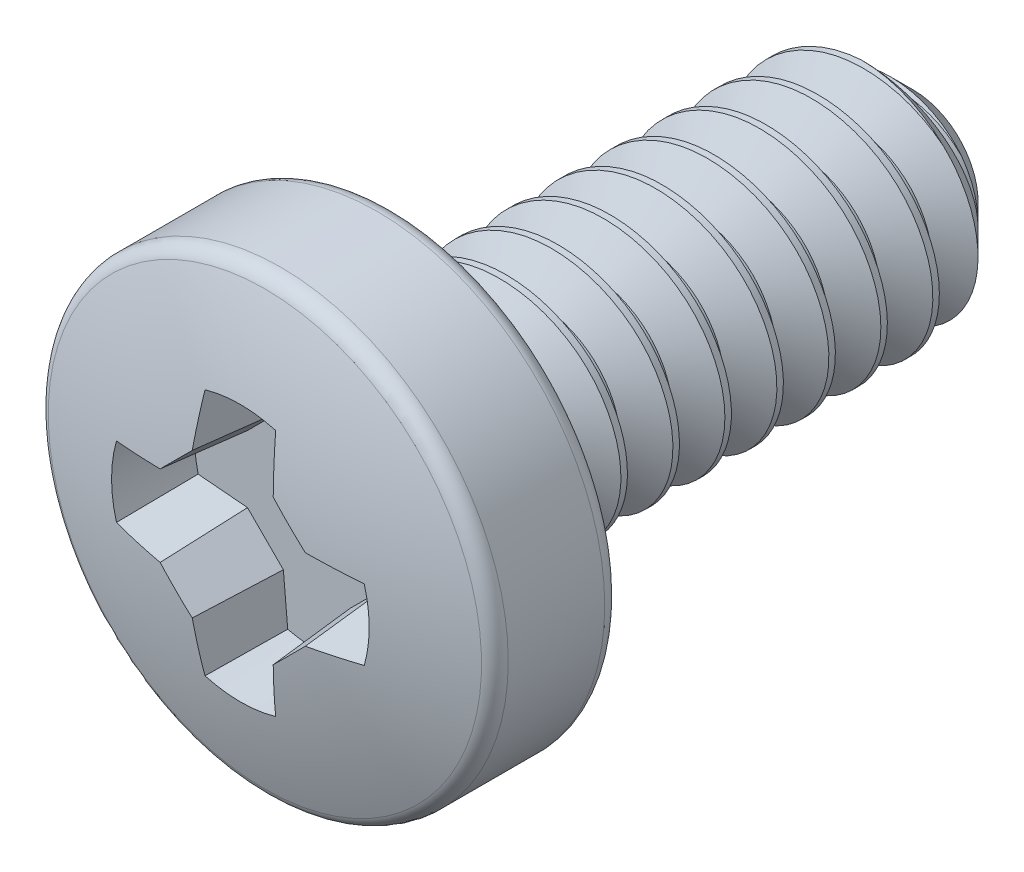
SolidWorks part; units mm, degrees
ref_plane "Front Plane" through (0, 0, 0) normal (0, 0, 1) x (1, 0, 0)
ref_plane "Top Plane" through (0, 0, 0) normal (0, 1, 0) x (1, 0, 0)
ref_plane "Right Plane" through (0, 0, 0) normal (1, 0, 0) x (0, 0, -1)
sketch "Layout_Sketch1" plane through (0, 0, 0) normal (1, 0, 0) x (0, 0, -1)
  line L0 (0, -2.7813) -> (0, 2.7813) construction
  line L1 (6.35, -1.4224) -> (6.35, 1.4224) construction
  line L2 (6.35, 0) -> (-2.032, 0) construction
  line L3 (-1.524, 2.7813) -> (0, 2.7813)
  line L4 (-1.524, -2.7813) -> (0, -2.7813)
  line L5 (6.35, 1.4224) -> (0, 1.4224) construction
  line L6 (6.35, -1.4224) -> (5.715, -1.4224) construction
  arc A0 (-1.524, -2.7813) -> (-1.524, 2.7813) centre (5.8358, 0) cw
  point P4 (0, 0)
  point P8 (6.35, 0)
  point P13 (5.3975, 0.4953)
  point P16 (5.715, -1.4224)
  point P17 (-0.9398, 0)
  point P18 (-0.635, 0)
  dimension "HeadDIA" = 5.5626
  dimension "HeadH" = 2.032
  dimension "D1" = 1.524
  dimension "ThreadOD" = 2.8448
  dimension "ThreadPitch" = 0.635
  dimension "D3" = 0.9525
  dimension "D2" = 0.635
  dimension "D4" = 0.3048
  dimension "D5" = 6.985
  dimension "ThreadLength" = 6.35
sketch "Sketch2" plane through (0, 0, 0) normal (1, 0, 0) x (0, 0, -1)
  line L0 (-1.524, 2.7813) -> (0, 2.7813)
  line L1 (0, 2.7813) -> (0, 1.4224)
  line L2 (0, 1.4224) -> (6.35, 1.4224)
  line L3 (6.35, 1.4224) -> (6.35, 0)
  line L4 (6.35, -1.4224) -> (6.35, 1.4224) construction
  line L5 (6.35, 0) -> (-2.032, 0)
  arc A0 (-2.032, 0) -> (-1.524, 2.7813) centre (5.8358, 0) cw
  arc A1 (-1.524, 2.7813) -> (-1.524, -2.7813) centre (5.8358, 0) ccw construction
revolve "Revolve1" add sketch "Sketch2" angle 360 about L5
ref_plane "Plane1" through (0, 0, 2.032) normal (0, 0, 1) x (1, 0, 0)
sketch "Sketch3" plane through (0, 0, 2.032) normal (0, 0, 1) x (1, 0, 0)
  line L0 (0, 0) -> (0, 0.889) construction
  line L1 (0, -2.7813) -> (0, 2.7813) construction
  line L2 (-0.4445, 0) -> (0.4445, 0) construction
  line L3 (0, 0) -> (1.5875, 0) construction
  line L4 (0.4445, 1.524) -> (0.5001, 0.889)
  line L5 (0.889, 0.5001) -> (1.524, 0.4445)
  line L6 (0, 0) -> (0.6286, 0.6286) construction
  line L7 (0.5001, 0.889) -> (0.889, 0.5001)
  line L8 (0.6945, 0.6945) -> (0.6286, 0.6286) construction
  line L9 (0.4445, 1.524) -> (0.4445, 0.7699) construction
  line L10 (0.889, -0.5001) -> (1.524, -0.4445)
  line L11 (0.5001, -0.889) -> (0.889, -0.5001)
  line L12 (0.4445, -1.524) -> (0.5001, -0.889)
  line L13 (-0.4445, -1.524) -> (-0.5001, -0.889)
  line L14 (-0.5001, -0.889) -> (-0.889, -0.5001)
  line L15 (-0.889, -0.5001) -> (-1.524, -0.4445)
  line L16 (-0.889, 0.5001) -> (-1.524, 0.4445)
  line L17 (-0.5001, 0.889) -> (-0.889, 0.5001)
  line L18 (-0.4445, 1.524) -> (-0.5001, 0.889)
  circle A0 centre (0, 0) radius 1.5875 construction
  circle A1 centre (0, 0) radius 0.889 construction
  arc A2 (-0.4445, 1.524) -> (0.4445, 1.524) centre (0, 0) cw
  arc A3 (1.524, 0.4445) -> (1.524, -0.4445) centre (0, 0) cw
  arc A4 (-1.524, 0.4445) -> (-1.524, -0.4445) centre (0, 0) ccw
  arc A5 (-0.4445, -1.524) -> (0.4445, -1.524) centre (0, 0) ccw
  point P9 (0, 0)
  point P21 (0, -1.5875)
  dimension "Phil_DIA" = 3.175
  dimension "Phil_W" = 0.889
  dimension "D1" = 45
  dimension "D2" = 0.889
  dimension "D3" = 5
extrude "Cut-Extrude1" cut sketch "Sketch3" against normal up to vertex (1.0922 mm away) draft 5 up to point (0, 0, 0.9398)
fillet "Fillet1" radius 0.2032 2 edges at (0, 2.7813, 0) (0, 2.7813, 1.524)
chamfer "Chamfer1" distance 0.635 angle 45 1 edges at (0, 1.4224, -6.35)
sketch "Sketch4" plane through (0, 0, 0) normal (1, 0, 0) x (0, 0, -1)
  line L0 (6.3103, 1.4911) -> (6.9453, 1.4911) construction
  line L1 (6.9453, 1.4911) -> (6.6278, 0.9412) construction
  line L2 (6.6278, 0.9412) -> (6.3103, 1.4911) construction
  line L3 (6.6278, 0.9412) -> (6.6278, 1.01) construction
  line L4 (6.6278, 1.01) -> (6.6278, 1.4224) construction
  line L5 (6.6278, 1.4224) -> (6.6278, 1.4911) construction
  line L6 (6.9255, 1.4568) -> (6.3302, 1.4568) construction
  line L7 (6.9056, 1.4224) -> (6.35, 1.4224) construction
  line L8 (6.6675, 1.01) -> (6.5881, 1.01) construction
  line L9 (6.3302, 1.4568) -> (6.9255, 1.4568)
  line L10 (6.9255, 1.4568) -> (6.6675, 1.01)
  line L11 (6.6675, 1.01) -> (6.5881, 1.01)
  line L12 (6.5881, 1.01) -> (6.3302, 1.4568)
  line L13 (6.35, -1.4224) -> (6.35, 1.4224) construction
  line L14 (6.35, 1.4224) -> (0, 1.4224) construction
  point P9 (6.6278, 1.4224)
  point P12 (6.6278, 1.4568)
  point P15 (6.6278, 1.01)
  dimension "D1" = 0.635
  dimension "D2" = 0.0794
sketch "Sketch5" plane through (0, 0, -6.35) normal (0, 0, -1) x (-1, 0, 0)
  circle A0 centre (0, 0) radius 1.4224
curve "Helix/Spiral1" pitch 0.635 height 6.985 radius 1.4224 centre (0, 0, -6.35) axis (0, 0, 1) start towards (0, 1, 0)
sweep "Cut-Sweep1" cut profiles "Sketch4" path "Helix/Spiral1" align with end faces yes
sketch "Sketch6" plane through (0, 0, 0) normal (0, 0, -1) x (-1, 0, 0)
  circle A0 centre (0, 0) radius 2.5781
  circle A1 centre (0, 0) radius 2.5781 construction
extrude "Boss-Extrude1" add sketch "Sketch6" against normal up to surface (0.9398 mm away) up to face at (0, 0, 0.9398)
sketch "Sketch7" plane through (0, 0, 0) normal (0, 0, -1) x (-1, 0, 0)
  line L0 (0, 2.7813) -> (0, -2.7813) construction
  circle A0 centre (0, 0) radius 1.4911
extrude "Boss-Extrude2" add sketch "Sketch7" along normal up to vertex (6.35 mm away) draft 20 up to point (0, 0, -6.35)
ref_plane "Contact Plane 1" through (0, 0, 0) normal (0, 0, -1) x (-1, 0, 0)
ref_plane "Contact Plane 2" through (0, 0, -6.35) normal (0, 0, -1) x (-1, 0, 0)
ref_axis "Center Axis 1" through (0, 0, -6.35) along (0, 0, 1)
equation "\"D1@Layout_Sketch1\" = \"HeadH@Layout_Sketch1\" * 0.75"
equation "\"D3@Layout_Sketch1\" = \"ThreadPitch@Layout_Sketch1\" * 1.5"
equation "\"D2@Layout_Sketch1\" = \"ThreadPitch@Layout_Sketch1\""
equation "\"D4@Layout_Sketch1\" = \"D1@Layout_Sketch1\" / 5"
equation "\"D2@Sketch3\"=\"Phil_W@Sketch3\""
equation "\"D1@Fillet1\"=\"HeadH@Layout_Sketch1\"/10"
equation "\"D1@Chamfer1\"=\"ThreadPitch@Layout_Sketch1\""
equation "\"D1@Sketch4\"=\"ThreadPitch@Layout_Sketch1\""
equation "\"D2@Sketch4\"=\"D1@Sketch4\"/8"
equation "\"D4@Helix/Spiral1\"=\"ThreadPitch@Layout_Sketch1\""
equation "\"D3@Helix/Spiral1\"=\"D5@Layout_Sketch1\""
